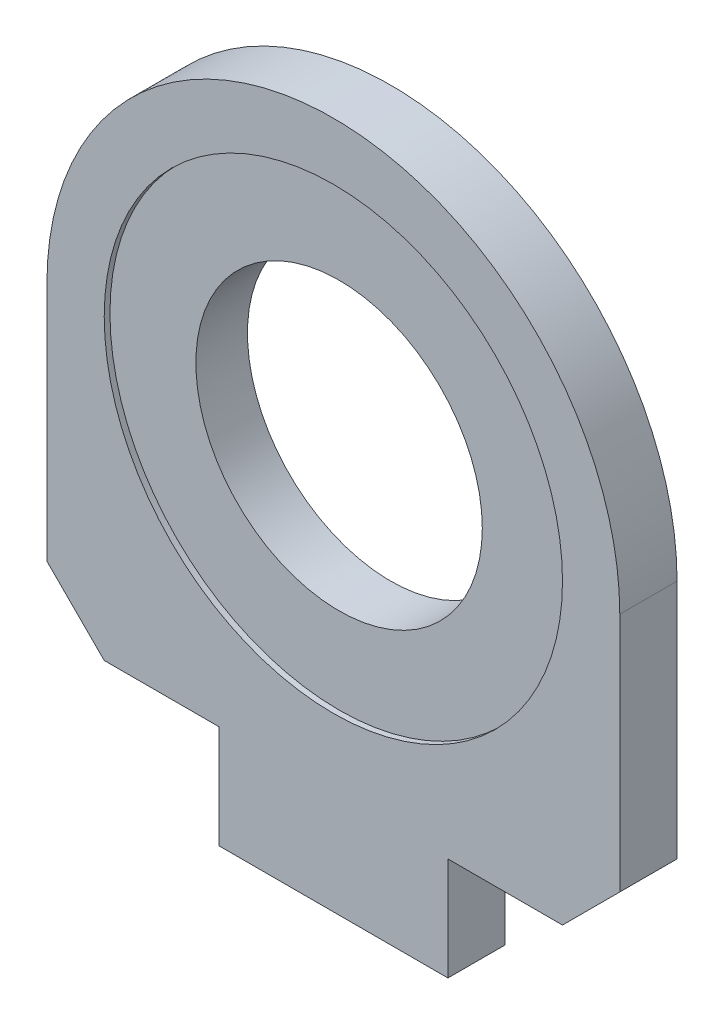
SolidWorks part; units mm, degrees
ref_plane "前基準面" through (0, 0, 0) normal (0, 0, 1) x (1, 0, 0)
ref_plane "上基準面" through (0, 0, 0) normal (0, 1, 0) x (1, 0, 0)
ref_plane "右基準面" through (0, 0, 0) normal (1, 0, 0) x (0, 0, -1)
sketch "草圖1" plane through (0, 0, 0) normal (0, 0, 1) x (1, 0, 0)
  line L0 (-50, 0) -> (-50, -42)
  line L1 (-50, -42) -> (-40, -52)
  line L2 (-40, -52) -> (-20, -52)
  line L3 (-20, -52) -> (-20, -70)
  line L4 (-20, -70) -> (20, -70)
  line L5 (0, 57.375) -> (0, -89.775) construction
  line L6 (20, -52) -> (20, -70)
  line L7 (40, -52) -> (20, -52)
  line L8 (50, -42) -> (40, -52)
  line L9 (50, 0) -> (50, -42)
  circle A0 centre (0, 0) radius 25
  circle A1 centre (0, 0) radius 40
  arc A2 (-50, 0) -> (50, 0) centre (0, 0) cw
  point P14 (0, -70)
  dimension "D4" = 50
  dimension "D5" = 80
  dimension "D6" = 50
  dimension "D1" = 18
  dimension "D2" = 40
  dimension "D3" = 52
  dimension "D7" = 45
  dimension "D8" = 10
extrude "填料-伸長1" add sketch "草圖1" along normal blind 10 contours L5 A2 L0 L1 L2 L3 L4 A1 | A2 L5 A1 L4 L6 L7 L8 L9 | A1 L5 A0 | L5 A1 A0 region at (-34.4361, 34.4361, 0) region at (34.4361, 34.4361, 0) region at (27.6518, 27.6518, 0) region at (-0.8944, 32.5, 0)
extrude "除料-伸長1" cut sketch "草圖1<4>" against normal blind 1 from surface contours L5 A1 A0 | A1 L5 A0 region at (27.6518, 27.6518, 0) region at (-0.8944, 32.5, 0) starting at face at (25, 0, 10)
sketch "草圖1<4>" plane through (0, 0, 0) normal (0, 0, 1) x (1, 0, 0) same geometry as "草圖1"
